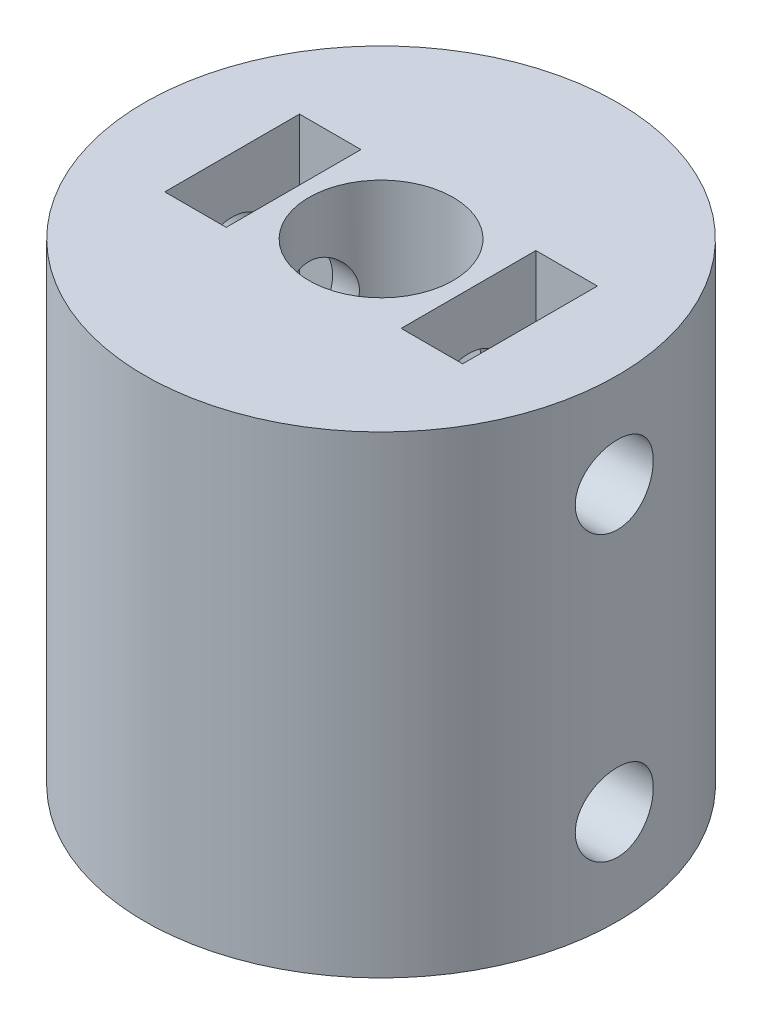
SolidWorks part; units mm, degrees
ref_plane "Plano frontal" through (0, 0, 0) normal (0, 0, 1) x (1, 0, 0)
ref_plane "Plano superior" through (0, 0, 0) normal (0, 1, 0) x (1, 0, 0)
ref_plane "Plano direito" through (0, 0, 0) normal (1, 0, 0) x (0, 0, -1)
sketch "Esboço1" plane through (0, 0, 0) normal (0, 0, 1) x (1, 0, 0)
  line L0 (3.05, 20) -> (10, 20)
  line L1 (10, 20) -> (10, 0)
  line L2 (10, 0) -> (2.4, 0)
  line L3 (2.4, 0) -> (2.4, 8)
  line L4 (2.4, 8) -> (3.05, 8)
  line L5 (3.05, 8) -> (3.05, 20)
  line L6 (0, 0) -> (0, 17.7118) construction
  dimension "D1" = 6.1
  dimension "D2" = 4.8
  dimension "D3" = 8
  dimension "D4" = 12
  dimension "D5" = 20
revolve "Revolução1" add sketch "Esboço1" angle 360 about L6
sketch "Esboço2" plane through (0, 20, 0) normal (0, 1, 0) x (1, 0, 0)
  line L0 (-5, 0) -> (5, 0) construction
  line L1 (0, 6.1548) -> (0, -5.7838) construction
  line L2 (3.7, -2.85) -> (6.3, -2.85)
  line L3 (3.7, -2.85) -> (3.7, 2.85)
  line L4 (3.7, 2.85) -> (6.3, 2.85)
  line L5 (6.3, -2.85) -> (6.3, 2.85)
  line L6 (3.7, -2.85) -> (6.3, 2.85) construction
  line L7 (3.7, 2.85) -> (6.3, -2.85) construction
  line L8 (-3.7, 2.85) -> (-6.3, -2.85) construction
  line L9 (-3.7, -2.85) -> (-6.3, 2.85) construction
  line L10 (-6.3, -2.85) -> (-6.3, 2.85)
  line L11 (-3.7, 2.85) -> (-6.3, 2.85)
  line L12 (-3.7, -2.85) -> (-3.7, 2.85)
  line L13 (-3.7, -2.85) -> (-6.3, -2.85)
  point P5 (0, 0)
  dimension "D1" = 2.6
  dimension "D2" = 5.7
  dimension "D3" = 10
extrude "Corte-extrusão1" cut sketch "Esboço2" against normal blind 8
extrude "Corte-extrusão2" cut sketch "Esboço2<2>" along normal blind 8 from surface starting at face at (0, 0, -10)
sketch "Esboço2<2>" plane through (0, 20, 0) normal (0, 1, 0) x (1, 0, 0) same geometry as "Esboço2"
sketch "Esboço3" plane through (-3.7, 0, 0) normal (-1, 0, 0) x (0, 0, 1)
  line L0 (0, 0) -> (0, 8) construction
  line L1 (-2.85, 0) -> (2.85, 0) construction
  line L2 (-2.85, 8) -> (2.85, 8) construction
  line L3 (0, 12) -> (0, 20) construction
  line L4 (2.85, 12) -> (-2.85, 12) construction
  line L5 (2.85, 20) -> (-2.85, 20) construction
  circle A0 centre (0, 4) radius 1.65
  circle A1 centre (0, 16) radius 1.65
  dimension "D1" = 3.3
extrude "Corte-extrusão3" cut sketch "Esboço3" against normal through all both and the other way through all
